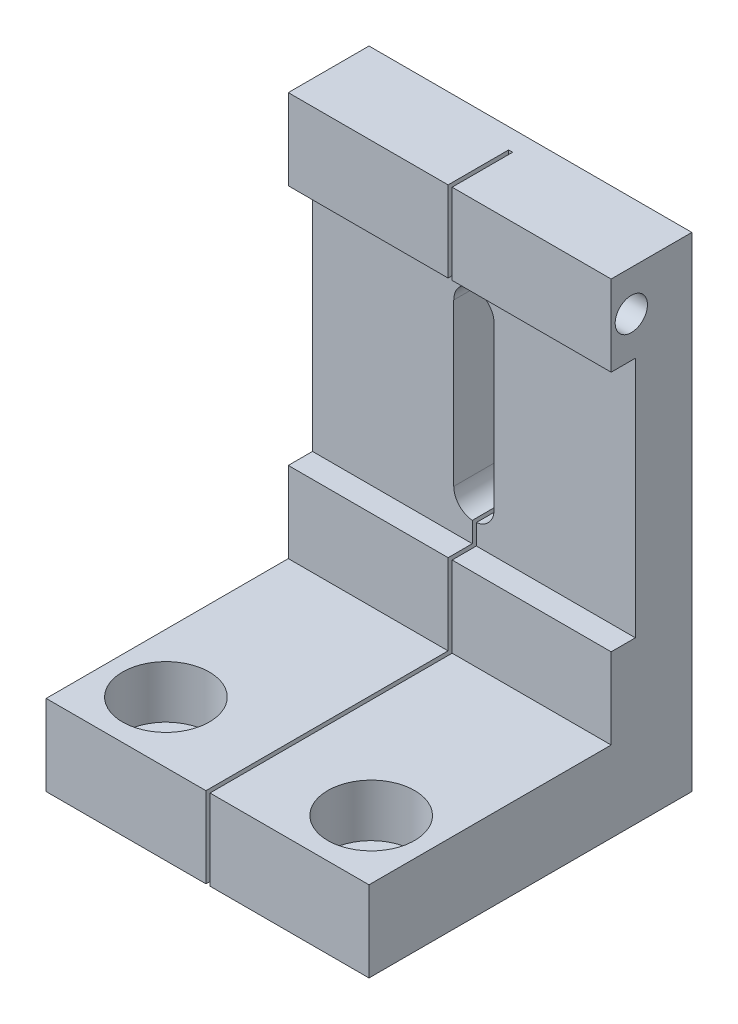
SolidWorks part; units mm, degrees
ref_plane "Front Plane" through (0, 0, 0) normal (0, 0, 1) x (1, 0, 0)
ref_plane "Top Plane" through (0, 0, 0) normal (0, 1, 0) x (1, 0, 0)
ref_plane "Right Plane" through (0, 0, 0) normal (1, 0, 0) x (0, 0, -1)
sketch "Sketch1" plane through (0, 0, 0) normal (0, 0, 1) x (1, 0, 0)
  line L1 (0, 0) -> (-40, 0)
  line L2 (0, 0) -> (0, -60)
  line L3 (0, -60) -> (-40, -60)
  line L4 (-40, 0) -> (-40, -60)
  dimension "D1" = 40
  dimension "D2" = 60
extrude "Boss-Extrude1" add sketch "Sketch1" along normal blind 10
sketch "Sketch2" plane through (0, 0, 10) normal (0, 0, 1) x (1, 0, 0)
  line L0 (-20, -15) -> (-20, -35) construction
  line L1 (-17.5, -15) -> (-17.5, -35)
  line L2 (-22.5, -15) -> (-22.5, -35)
  line L4 (-40, -60) -> (0, -60) construction
  line L5 (0, 0) -> (-40, 0) construction
  line L6 (-20, 0) -> (-20, -5.6142) construction
  arc A0 (-17.5, -15) -> (-22.5, -15) centre (-20, -15) ccw
  arc A1 (-22.5, -35) -> (-17.5, -35) centre (-20, -35) ccw
  point P2 (-20, -25)
  dimension "D1" = 5
  dimension "D2" = 20
  dimension "D4" = 35
extrude "Cut-Extrude1" cut sketch "Sketch2" against normal through all
sketch "Sketch5" plane through (0, 0, 0) normal (1, 0, 0) x (0, 0, -1)
  line L0 (-7, -10) -> (-10, -10)
  line L1 (-10, -60) -> (-10, 0) construction
  line L2 (-7, -10) -> (-7, -40)
  line L3 (-10, -60) -> (0, -60) construction
  line L4 (-7, -40) -> (-10, -40)
  line L7 (-10, -10) -> (-10, -40)
  dimension "D1" = 3
  dimension "D4" = 30
  dimension "D5" = 20
extrude "Cut-Extrude4" cut sketch "Sketch5" against normal through all
sketch "Sketch6" plane through (0, 0, 10) normal (0, 0, 1) x (1, 0, 0)
  line L0 (-40, -40) -> (-40, -60) construction
  line L1 (0, -60) -> (-40, -60)
  line L2 (0, -60) -> (0, -50)
  line L3 (0, -50) -> (-40, -50)
  line L4 (-40, -60) -> (-40, -50)
  dimension "D1" = 10
extrude "Boss-Extrude2" add sketch "Sketch6" along normal blind 30
sketch "Sketch7" plane through (0, -50, 0) normal (0, 1, 0) x (1, 0, 0)
  line L3 (-40, -40) -> (-40, -10) construction
  circle A0 centre (-4.0875, -15.1829) radius 2
  circle A1 centre (-35.875, -15.1829) radius 2
  dimension "D1" = 4
  dimension "D2" = 4
  dimension "D3" = 4.125
  dimension "D5" = 31.7875
extrude "Cut-Extrude5" [suppressed] cut sketch "Sketch7" against normal blind 40
sketch "Sketch8" plane through (0, 0, 0) normal (0, 1, 0) x (1, 0, 0)
  line L0 (0, -10) -> (-40, -10) construction
  line L2 (-20.2, -40) -> (-19.7, -40)
  line L5 (-20.2, -40) -> (-20.2, -2.5)
  line L7 (0, -40) -> (-40, -40) construction
  line L9 (-20.2, -2.5) -> (-19.7, -2.5)
  line L10 (-19.7, -40) -> (-19.7, -2.5)
  line L11 (-22.5, 0) -> (-22.5, -7) construction
  dimension "D1" = 0.5
  dimension "D2" = 2.3
  dimension "D3" = 7.5
extrude "Cut-Extrude7" cut sketch "Sketch8" against normal up to surface (60 mm away) up to face at (-20, -60, 20)
sketch "Sketch9" plane through (0, -60, 0) normal (0, -1, 0) x (1, 0, 0)
  line L3 (0, 40) -> (0, 0) construction
  line L5 (-40, 7) -> (-20.2, 7) construction
  circle A0 centre (-32.73, 5) radius 2
  circle A1 centre (-7.3, 5) radius 2
  dimension "D1" = 4
  dimension "D3" = 7.3
  dimension "D4" = 4
  dimension "D2" = 25.43
extrude "Cut-Extrude9" [suppressed] cut sketch "Sketch9" against normal blind 15
sketch "Sketch10" plane through (0, 0, 0) normal (1, 0, 0) x (0, 0, -1)
  line L1 (-10, 0) -> (0, 0) construction
  line L2 (-10, -10) -> (-10, 0) construction
  circle A0 centre (-7.5, -5) radius 2
  dimension "D1" = 4
  dimension "D2" = 5
  dimension "D3" = 2.5
extrude "Cut-Extrude10" cut sketch "Sketch10" against normal blind 30
sketch "Sketch12" plane through (0, -60, 0) normal (0, -1, 0) x (1, 0, 0)
  line L0 (-32.73, 32.43) -> (-32.73, 7) construction
  line L1 (-32.73, 7) -> (-7.3, 7) construction
  line L2 (-7.3, 7) -> (-7.3, 32.43) construction
  line L3 (-7.3, 32.43) -> (-32.73, 32.43) construction
  line L5 (-40, 7) -> (-20.2, 7) construction
  line L6 (0, 40) -> (0, 0) construction
  line L10 (-19.7, 40) -> (0, 40) construction
  line L11 (-40, 0) -> (-40, 40) construction
  circle A0 centre (-7.3, 32.43) radius 3.4
  circle A1 centre (-32.73, 32.43) radius 3.4
  circle A2 centre (-32.73, 7) radius 2.49
  circle A3 centre (-7.3, 7) radius 2.49
  circle A4 centre (-7.3, 32.43) radius 5.375 construction
  circle A5 centre (-32.73, 7.03) radius 3.4 [skipped]
  circle A6 centre (-7.3, 7.03) radius 3.4 [skipped]
  dimension "D1" = 6.8
  dimension "D2" = 2
  dimension "D3" = 2
  dimension "D4" = 10.75
  dimension "D6" = 7.3
  dimension "D7" = 25.43
  dimension "D8" = 4.98
  dimension "D9" = 25.43
  dimension "D11" = 7.57
  dimension "D5" = 2
  dimension "D12" = 7.27
extrude "Cut-Extrude13" cut sketch "Sketch12" against normal up to surface (10 mm away) up to face at (-9.85, -50, 25)
sketch "Sketch14" plane through (0, -50, 0) normal (0, 1, 0) x (1, 0, 0)
  line L0 (-32.73, -32.43) -> (18.13, -32.43) construction
  circle A0 centre (-32.73, -32.43) radius 5.375
  circle A1 centre (-7.3, -32.43) radius 5.375
  dimension "D1" = 10.75
  dimension "D3" = 25.43
  dimension "D2" = 2
extrude "Cut-Extrude14" cut sketch "Sketch14" against normal blind 6.5
equation "\"inch\"= 25.43"
equation "\"D5@Sketch7\"=\"inch\"*1.25"
equation "\"D2@Sketch9\"=\"inch\""
equation "\"D7@Sketch12\"=\"inch\""
equation "\"D3@Sketch14\" = \"inch\""
equation "\"D9@Sketch12\"=\"inch\""
